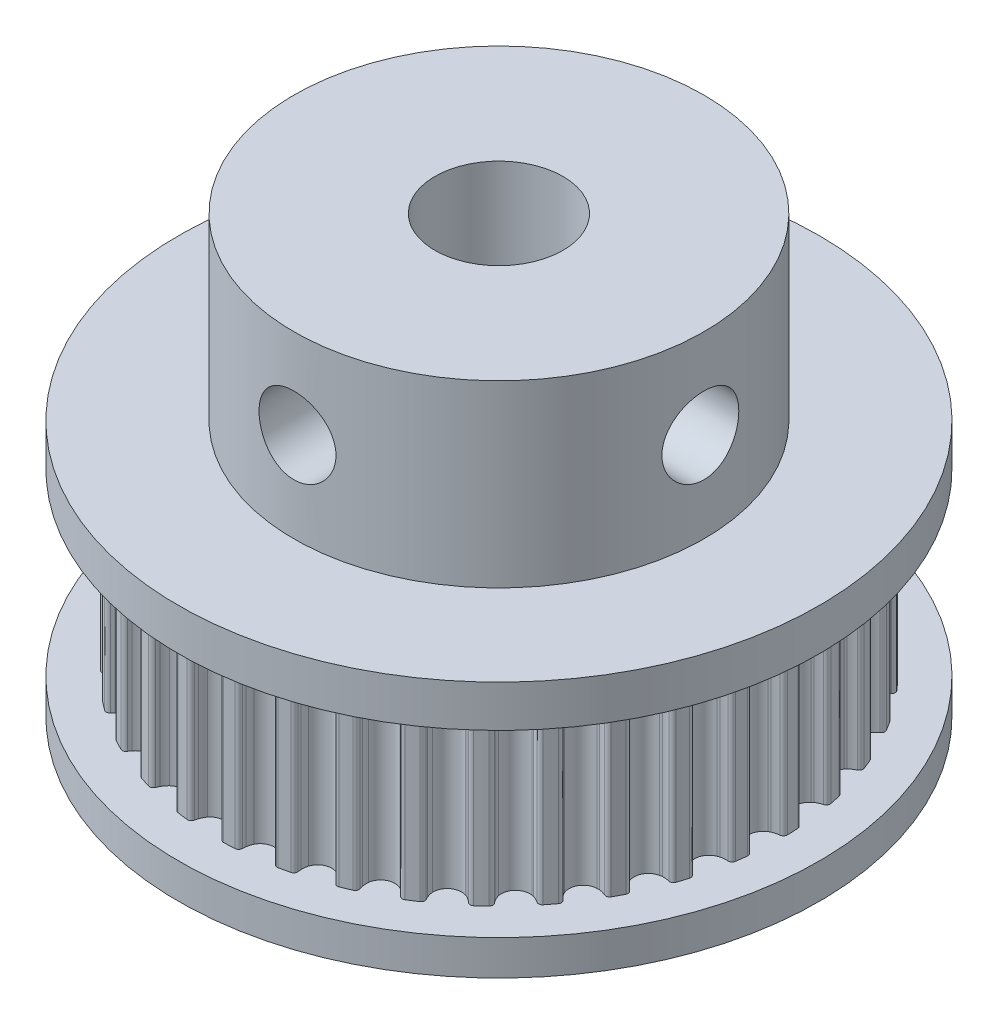
SolidWorks part; units mm, degrees
ref_plane "Płaszczyzna przednia" through (0, 0, 0) normal (0, 0, 1) x (1, 0, 0)
ref_plane "Płaszczyzna górna" through (0, 0, 0) normal (0, 1, 0) x (1, 0, 0)
ref_plane "Płaszczyzna prawa" through (0, 0, 0) normal (1, 0, 0) x (0, 0, -1)
sketch "Sketch1" plane through (0, 0, 0) normal (0, 0, 1) x (1, 0, 0)
  line L0 (0, 0) -> (0, 10.7402) construction
  line L1 (2.5, 0) -> (12.5, 0)
  line L2 (12.5, 0) -> (12.5, 1.3674)
  line L3 (12.5, 1.3674) -> (11, 1.3674)
  line L4 (11, 1.3674) -> (11, 8.3674)
  line L5 (11, 8.3674) -> (12.5, 8.3674)
  line L6 (12.5, 8.3674) -> (12.5, 10)
  line L7 (12.5, 10) -> (8, 10)
  line L8 (8, 10) -> (8, 17)
  line L9 (8, 17) -> (2.5, 17)
  line L10 (2.5, 17) -> (2.5, 0)
  dimension "D1" = 2.5
  dimension "D2" = 12.5
  dimension "D3" = 8.5
  dimension "D4" = 10
  dimension "D5" = 7
  dimension "D6" = 10
  dimension "D7" = 17
  dimension "D8" = 8
revolve "Revolve1" add sketch "Sketch1" angle 360 about L0
ref_plane "Plane2" through (0, 8.3674, 0) normal (0, -1, 0) x (-1, 0, 0)
sketch "Sketch3" plane through (0, 8.3674, 0) normal (0, -1, 0) x (-1, 0, 0)
  circle A0 centre (0, 0) radius 11
  circle A1 centre (0, 0) radius 2.5
  circle A2 centre (0, 0) radius 2.5
  circle A3 centre (0, 0) radius 11
sketch "Sketch5" plane through (0, 8.3674, 0) normal (0, -1, 0) x (-1, 0, 0)
  line L0 (0, 0) -> (7.4152, 7.4261) construction
  line L1 (0, 0) -> (8.0455, 6.7611) construction
  line L4 (0, 0) -> (9.006, 6.316) construction
  arc A1 (8.4213, 7.0769) -> (7.7724, 7.7839) centre (0, 0) ccw
  arc A2 (7.4152, 7.4261) -> (8.0455, 6.7611) centre (7.9577, 7.3091) ccw
  arc A3 (7.6868, 7.8685) -> (7.5189, 7.6635) centre (8.3696, 7.1379) ccw
  arc A4 (8.133, 6.7749) -> (8.498, 6.9846) centre (7.8286, 7.7275) ccw
  arc A6 (8.0455, 6.7611) -> (8.133, 6.7749) centre (8.0143, 7.2403) ccw
  arc A7 (8.498, 6.9846) -> (7.6868, 7.8685) centre (0, 0) ccw
  arc A8 (7.4152, 7.4261) -> (7.5189, 7.6635) centre (8.2998, 7.181) cw
  dimension "D2" = 22
  dimension "D4" = 2
  dimension "D5" = 5
  dimension "D6" = 2
  dimension "D8" = 22
  dimension "D3" = 5
  dimension "D9" = 11
extrude "Cut-Extrude1" cut sketch "Sketch5" along normal blind 7 contours A8 A2 A6 A4 A7 A1 A3 region at (-7.8642, 8.3674, -7.2186)
fillet "Fillet4" radius 0.15 2 edges at (-7.6868, 4.8674, -7.8685) (-8.498, 4.8674, -6.9846)
pattern_circular "CirPattern1" count 36 over 360 about axis through (0, 0, 0) along (0, -1, 0) of "Cut-Extrude1", "Fillet4" reverse direction yes
hole_wizard "Ø3.0mm Dowel Hole1" positions "Sketch7" profile "Sketch9" hole size "Ø3.0" standard "ANSI Metric" end condition up to next
sketch "Sketch7" plane through (0, 0, 0) normal (1, 0, 0) x (0, 0, -1)
  line L0 (2.5, 17) -> (-2.5, 17) construction
  point P0 (0, 13.5)
  dimension "D1" = 3.5
sketch "Sketch9" plane through (0, 13.5, 0) normal (0, 1, 0) x (0, 0, 1)
  line L0 (0, 0) -> (0, 8)
  line L1 (0, 8) -> (1.5, 8)
  line L2 (1.5, 8) -> (1.5, 0)
  line L5 (1.5, 0) -> (0, 0)
  line L11 (0, -6.35) -> (0, 107.95) construction
  dimension "Thru Hole Dia." = 3
  dimension "Thru Hole Depth" = 8
hole_wizard "Ø3.0mm Dowel Hole2" positions "Sketch10" profile "Sketch11" hole size "Ø3.0" standard "ANSI Metric" end condition up to next
sketch "Sketch10" plane through (0, 0, 0) normal (0, 0, 1) x (1, 0, 0)
  line L0 (2.5, 17) -> (-2.5, 17) construction
  point P0 (0, 13.5)
  dimension "D1" = 3.5
sketch "Sketch11" plane through (0, 13.5, 0) normal (1, 0, 0) x (0, 1, 0)
  line L0 (0, 0) -> (0, 8)
  line L1 (0, 8) -> (1.5, 8)
  line L2 (1.5, 8) -> (1.5, 0)
  line L5 (1.5, 0) -> (0, 0)
  line L11 (0, -6.35) -> (0, 107.95) construction
  dimension "Thru Hole Dia." = 3
  dimension "Thru Hole Depth" = 8
